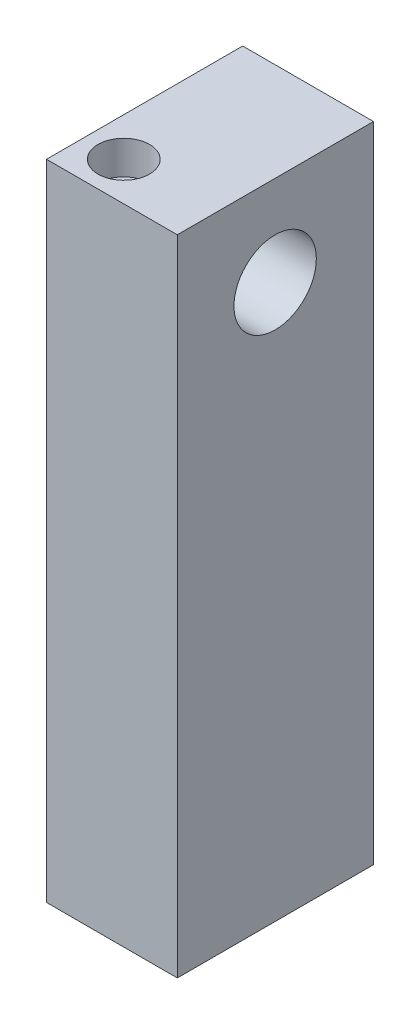
SolidWorks part; units mm, degrees
ref_plane "Front Plane" through (0, 0, 0) normal (0, 0, 1) x (1, 0, 0)
ref_plane "Top Plane" through (0, 0, 0) normal (0, 1, 0) x (1, 0, 0)
ref_plane "Right Plane" through (0, 0, 0) normal (1, 0, 0) x (0, 0, -1)
sketch "Sketch1" plane through (0, 0, 0) normal (0, 1, 0) x (1, 0, 0)
  line L1 (0, 0) -> (50.8, 0)
  line L2 (0, 0) -> (0, 76.2)
  line L3 (0, 76.2) -> (50.8, 76.2)
  line L4 (50.8, 0) -> (50.8, 76.2)
  dimension "D1" = 50.8
  dimension "D2" = 76.2
extrude "Boss-Extrude1" add sketch "Sketch1" along normal blind 250
sketch "Sketch2" plane through (50.8, 0, 0) normal (1, 0, 0) x (0, 0, -1)
  line L1 (0, 0) -> (38, 0)
  line L2 (0, 0) -> (0, 215)
  line L3 (0, 215) -> (38, 215)
  line L4 (38, 0) -> (38, 215)
  circle A0 centre (38, 215) radius 16
  dimension "D1" = 38
  dimension "D2" = 215
extrude "Cut-Extrude1" cut sketch "Sketch2" against normal blind 150 contours L4 A0 L3 | L3 A0 L4 region at (50.8, 208.2094, -31.2094) region at (50.8, 217.2635, -40.2635)
sketch "Sketch4" plane through (0, 250, 0) normal (0, 1, 0) x (1, 0, 0)
  line L5 (50.8, 0) -> (15, 0)
  line L6 (50.8, 0) -> (50.8, 15)
  line L7 (50.8, 15) -> (15, 15)
  line L8 (15, 0) -> (15, 15)
  circle A0 centre (15, 15) radius 5.25
  dimension "D1" = 35.8
  dimension "D2" = 15
extrude "Cut-Extrude3" cut sketch "Sketch4" against normal blind 60 contours A0
sketch "Sketch6" plane through (0, 250, 0) normal (0, 1, 0) x (1, 0, 0)
  circle A1 centre (15, 15) radius 10
extrude "Cut-Extrude4" cut sketch "Sketch6" against normal blind 13
